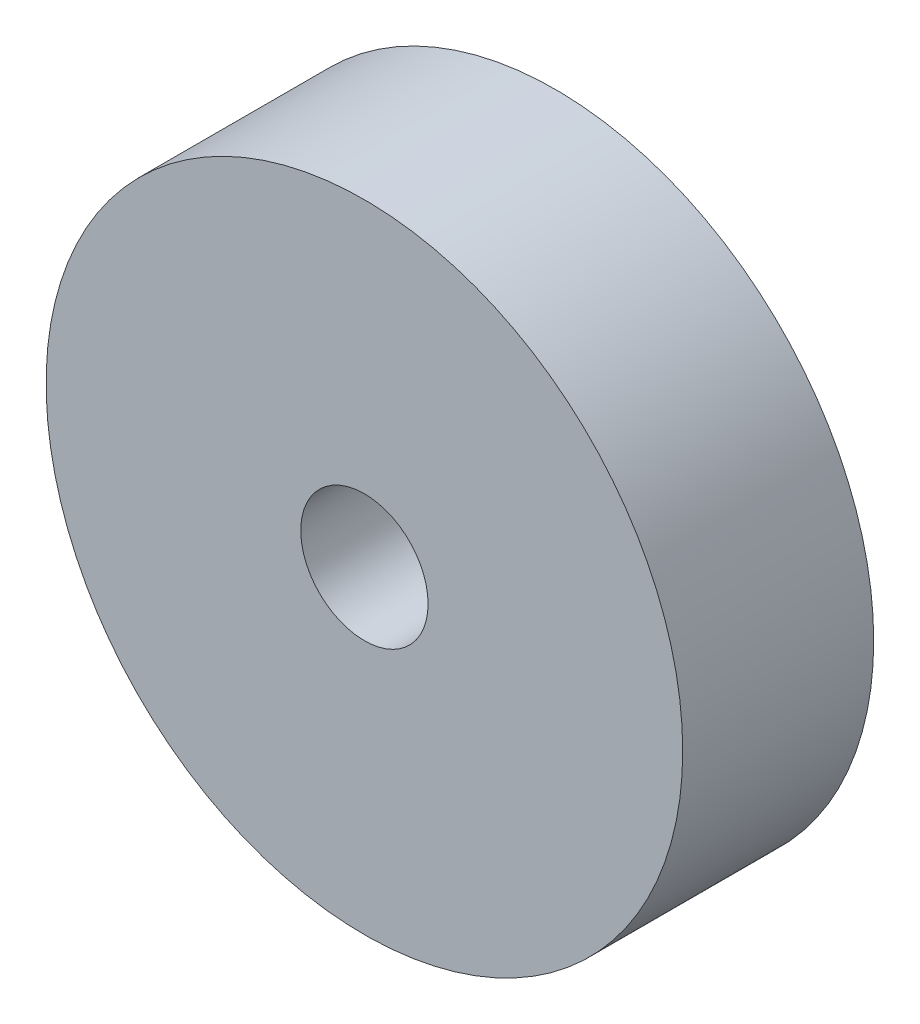
SolidWorks part; units mm, degrees
ref_plane "Front Plane" through (0, 0, 0) normal (0, 0, 1) x (1, 0, 0)
ref_plane "Top Plane" through (0, 0, 0) normal (0, 1, 0) x (1, 0, 0)
ref_plane "Right Plane" through (0, 0, 0) normal (1, 0, 0) x (0, 0, -1)
sketch "Sketch1" plane through (0, 0, 0) normal (0, 0, 1) x (1, 0, 0)
  circle A0 centre (0, 0) radius 10
  circle A1 centre (0, 0) radius 2
  dimension "D1" = 4
  dimension "D2" = 20
extrude "Boss-Extrude1" add sketch "Sketch1" along normal blind 6
